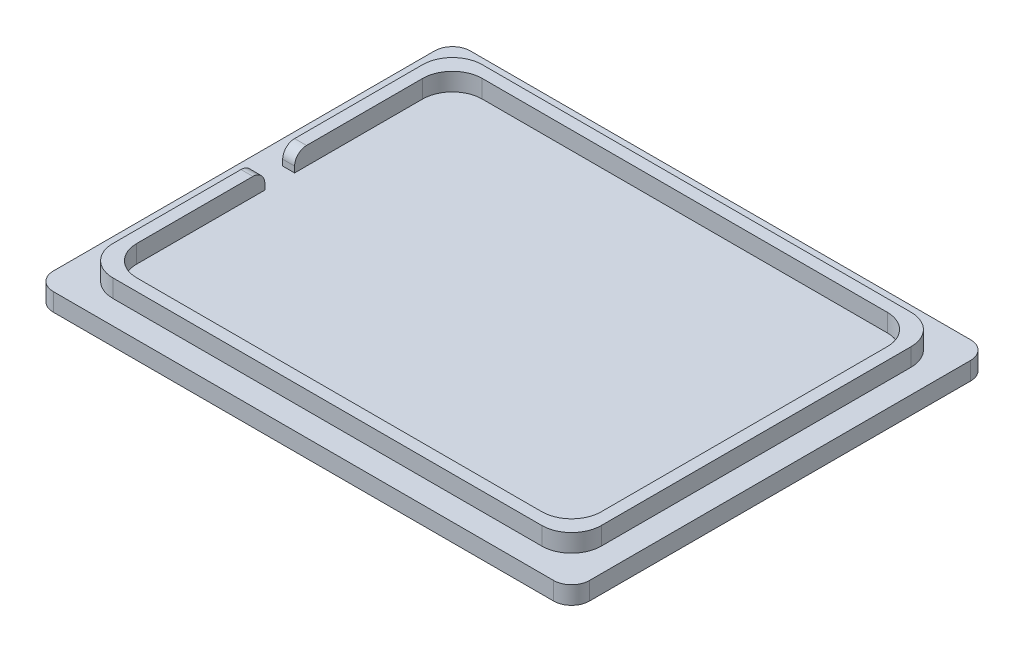
SolidWorks part; units mm, degrees
ref_plane "Plano frontal" through (0, 0, 0) normal (0, 0, 1) x (1, 0, 0)
ref_plane "Plano superior" through (0, 0, 0) normal (0, 1, 0) x (1, 0, 0)
ref_plane "Plano direito" through (0, 0, 0) normal (1, 0, 0) x (0, 0, -1)
sketch "Esboço1" plane through (0, 0, 0) normal (0, 1, 0) x (1, 0, 0)
  line L0 (-4, 4) -> (-86, 4)
  line L1 (0, 0) -> (-90, 0)
  line L2 (0, 0) -> (0, 70)
  line L3 (0, 70) -> (-90, 70)
  line L4 (-90, 0) -> (-90, 70)
  line L5 (-86, 4) -> (-86, 66)
  line L6 (-4, 66) -> (-86, 66)
  line L7 (-4, 4) -> (-4, 66)
  line L8 (-6, 6) -> (-84, 6)
  line L9 (-84, 6) -> (-84, 64)
  line L10 (-6, 64) -> (-84, 64)
  line L11 (-6, 6) -> (-6, 64)
  dimension "D1" = 90
  dimension "D2" = 70
  dimension "D3" = 4
  dimension "D4" = 2
extrude "Ressalto-extrusão1" add sketch "Esboço1" along normal blind 3 contours L4 L1 L2 L3 L7 L0 L5 L6 | L8 L11 L10 L9 | L0 L7 L6 L5 L11 L8 L9 L10 region at (-45, 0, -5.028) region at (-45, 0, -1.1402) region at (-45, 0, -35)
extrude "Ressalto-extrusão2" add sketch "Esboço1<3>" along normal blind 6 contours L0 L7 L6 L5 L11 L8 L9 L10 region at (-45, 0, -5.028)
sketch "Esboço1<3>" plane through (0, 0, 0) normal (0, 1, 0) x (1, 0, 0) same geometry as "Esboço1"
fillet "Filete1" radius 3 4 edges at (-90, 1.5, 0) (0, 1.5, 0) (0, 1.5, -70) (-90, 1.5, -70)
fillet "Filete2" radius 5 8 edges at (-84, 4.5, -6) (-86, 4.5, -4) (-4, 4.5, -4) (-6, 4.5, -6) (-6, 4.5, -64) (-4, 4.5, -66) (-84, 4.5, -64) (-86, 4.5, -66)
sketch "Esboço2" plane through (-86, 0, 0) normal (-1, 0, 0) x (0, 0, 1)
  line L1 (-32.5, 6) -> (-37.5, 6)
  line L3 (-32.5, 3) -> (-37.5, 3)
  line L4 (-37.5, 6) -> (-37.5, 3)
  line L5 (-3, 3) -> (-67, 3) construction
  line L6 (-32.5, 6) -> (-32.5, 3)
extrude "Corte-extrusão1" cut sketch "Esboço2" against normal up to next
fillet "Filete3" radius 2 2 edges at (-85, 6, -32.5) (-85, 6, -37.5)
